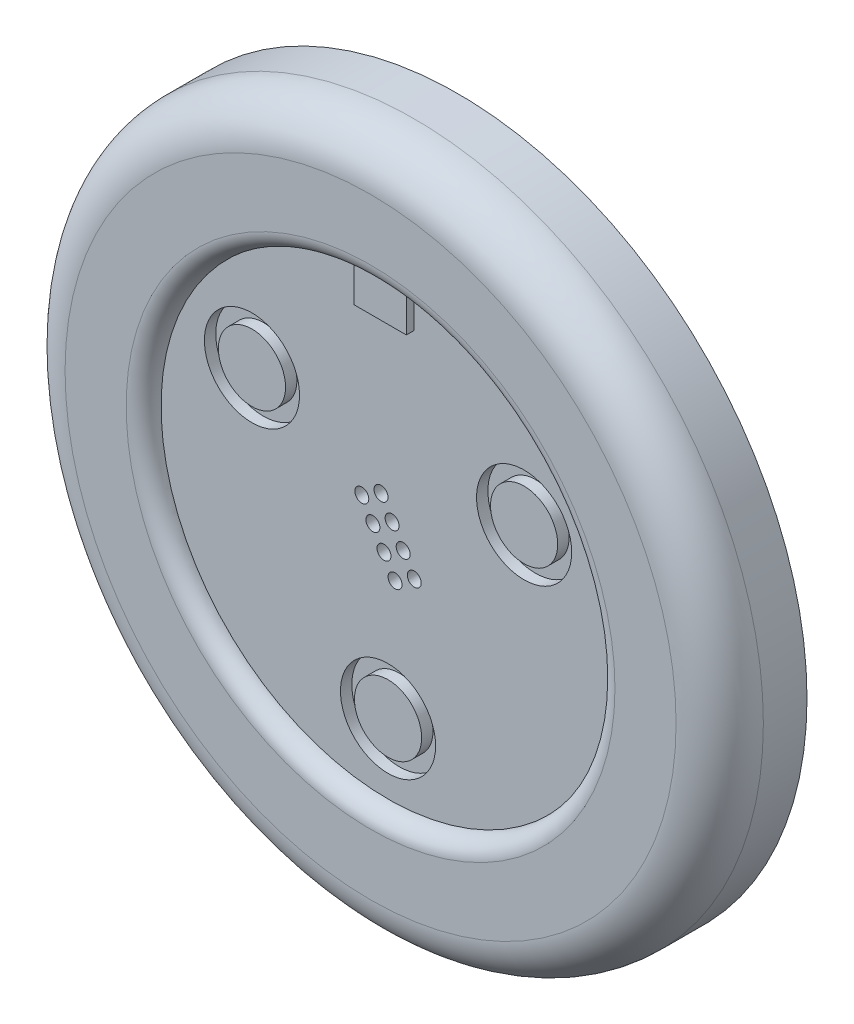
SolidWorks part; units mm, degrees
ref_plane "前视基准面" through (0, 0, 0) normal (0, 0, 1) x (1, 0, 0)
ref_plane "上视基准面" through (0, 0, 0) normal (0, 1, 0) x (1, 0, 0)
ref_plane "右视基准面" through (0, 0, 0) normal (1, 0, 0) x (0, 0, -1)
sketch "草图1" plane through (0, 0, 0) normal (0, 0, 1) x (1, 0, 0)
  circle A0 centre (0, 0) radius 40
extrude "凸台-拉伸1" add sketch "草图1" along normal blind 10
sketch "草图3" plane through (0, 0, 10) normal (0, 0, 1) x (1, 0, 0)
  circle A0 centre (0, 0) radius 26
extrude "切除-拉伸1" cut sketch "草图3" against normal blind 2
fillet "圆角2" radius 5 1 edges at (40, 0, 10)
sketch "草图7" plane through (0, 0, 8) normal (0, 0, 1) x (1, 0, 0)
  line L0 (0, 0) -> (0, -18) construction
  circle A1 centre (0, -18) radius 3.85
  circle A2 centre (0, -18) radius 5.45
  circle A3 centre (-15.5885, 9) radius 3.85
  circle A4 centre (-15.5885, 9) radius 5.45
  circle A5 centre (15.5885, 9) radius 3.85
  circle A6 centre (15.5885, 9) radius 5.45
  dimension "D1" = 3
  dimension "D2" = 18
extrude "切除-拉伸3" cut sketch "草图7" against normal blind 1.3
shell "抽壳2" thickness 2 removed face at (40, 0, 0)
sketch "草图9" plane through (0, 0, 8) normal (0, 0, -1) x (-1, 0, 0)
  line L2 (0, 0) -> (0, -30) construction
  circle A1 centre (0, -30) radius 1
  circle A2 centre (0, -30) radius 3
  circle A9 centre (-25.9808, 15) radius 3
  circle A10 centre (-25.9808, 15) radius 1
  circle A11 centre (25.9808, 15) radius 3
  circle A12 centre (25.9808, 15) radius 1
  dimension "D6" = 30
  dimension "D5" = 3
extrude "凸台-拉伸2" add sketch "草图9" along normal blind 8 separate body
sketch "草图10" plane through (0, 0, 8) normal (0, 0, 1) x (1, 0, 0)
  line L1 (0, 22) -> (3, 22)
  line L2 (3, 22) -> (3, 27)
  line L3 (3, 27) -> (-3, 27)
  line L4 (-3, 27) -> (-3, 22)
  line L5 (-3, 22) -> (0, 22)
extrude "凸台-拉伸5" add sketch "草图10" along normal blind 0.9 separate body
sketch "草图11" plane through (0, 0, 0) normal (0, 0, -1) x (-1, 0, 0)
  circle A0 centre (0, 0) radius 33.9006
extrude "切除-拉伸5" cut sketch "草图11" against normal blind 1.5
fillet "圆角3" radius 2 1 edges at (26, 0, 10)
sketch "草图12" plane through (0, 0, 8) normal (0, 0, 1) x (1, 0, 0)
  circle A1 centre (-0.8051, 3.9346) radius 0.8
  circle A2 centre (0.4649, 1.7349) radius 0.8
  circle A3 centre (1.7349, -0.4649) radius 0.8
  circle A4 centre (3.0049, -2.6646) radius 0.8
  circle A5 centre (-1.7349, 0.4649) radius 0.8
  circle A6 centre (-0.4649, -1.7349) radius 0.8
  circle A7 centre (0.8051, -3.9346) radius 0.8
  circle A8 centre (-3.0049, 2.6646) radius 0.8
  dimension "D1" = 4
  dimension "D2" = 2
extrude "切除-拉伸6" cut sketch "草图12" against normal blind 10
